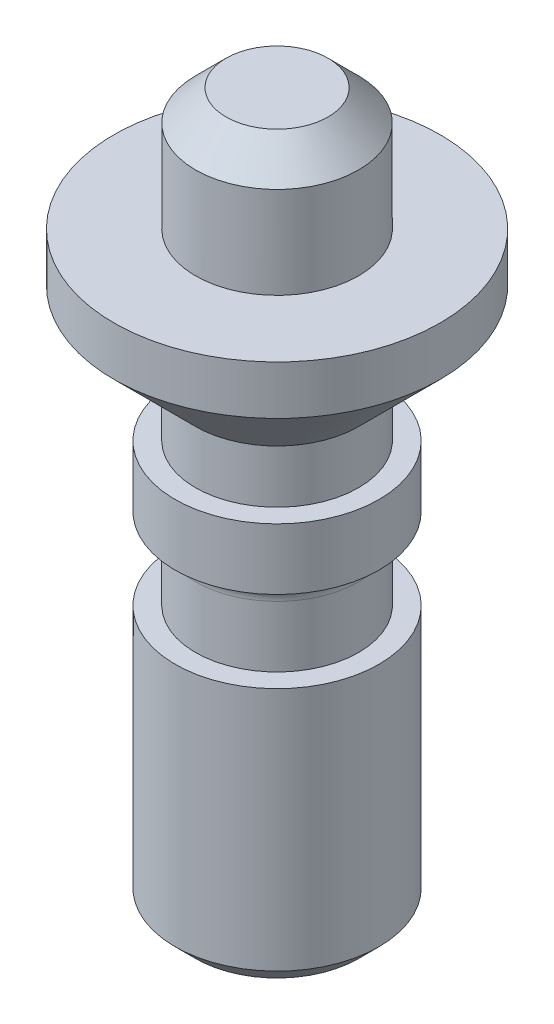
SolidWorks part; units mm, degrees
ref_plane "Front Plane" through (0, 0, 0) normal (0, 0, 1) x (1, 0, 0)
ref_plane "Top Plane" through (0, 0, 0) normal (0, 1, 0) x (1, 0, 0)
ref_plane "Right Plane" through (0, 0, 0) normal (1, 0, 0) x (0, 0, -1)
sketch "Sketch1" plane through (0, 0, 0) normal (0, 0, 1) x (1, 0, 0)
  line L0 (0, -103.4203) -> (0, 5067.5948) construction
  line L1 (0, 0) -> (2.5, 0)
  line L2 (2.5, 0) -> (2.5, 6.5)
  line L3 (2.5, 6.5) -> (2, 6.5)
  line L4 (2, 6.5) -> (2, 8.5)
  line L5 (2, 8.5) -> (2.5, 8.5)
  line L6 (2.5, 8.5) -> (2.5, 10)
  line L7 (2.5, 10) -> (2, 10)
  line L8 (2, 10) -> (2, 11.3)
  line L9 (2, 11.3) -> (4, 13.3)
  line L10 (4, 13.3) -> (4, 14.5)
  line L11 (4, 14.5) -> (2, 14.5)
  line L12 (2, 14.5) -> (2, 17.5)
  line L13 (2, 17.5) -> (0, 17.5)
  line L14 (0, 17.5) -> (0, 0)
  point P16 (1, 17.5)
  dimension "D1" = 17.5
  dimension "D2" = 3
  dimension "D3" = 4.2
  dimension "D4" = 6.5
  dimension "D5" = 8.5
  dimension "D6" = 1.5
  dimension "D7" = 1.3
  dimension "D8" = 45
  dimension "D9" = 2.5
  dimension "D10" = 2
  dimension "D11" = 2.5
  dimension "D12" = 2
  dimension "D13" = 4
  dimension "D14" = 2
revolve "Revolve1" add sketch "Sketch1" angle 360 about L0
fillet "Fillet1" radius 0.5 1 edges at (2, 8.5, 0)
chamfer "Chamfer1" distance 0.5 angle 45 1 edges at (2.5, 0, 0)
chamfer "Chamfer2" distance 0.75 angle 45 1 edges at (2, 17.5, 0)
sketch "Sketch4" plane through (0, 0, 0) normal (0, -1, 0) x (1, 0, 0)
  circle A0 centre (0, 0) radius 1.5
  dimension "D1" = 3
extrude "Cut-Extrude2" cut sketch "Sketch4" against normal blind 8.5 contours A0
sketch "Sketch6" plane through (0, 0, 0) normal (0, -1, 0) x (1, 0, 0)
  line L0 (-0.5, 1.4142) -> (-0.5, 1.1456)
  line L1 (0.5, 1.4142) -> (0.5, 1.1456)
  arc A0 (0.5, 1.1456) -> (-0.5, 1.1456) centre (0, 0) ccw
  circle A1 centre (0, 0) radius 1.5 construction
  arc A2 (0.5, 1.4142) -> (-0.5, 1.4142) centre (0, 0) ccw
  dimension "D1" = 2.5
  dimension "D2" = 0.5
  dimension "D3" = 0.5
extrude "Boss-Extrude1" add sketch "Sketch6" against normal blind 8.5
pattern_circular "CirPattern1" count 4 over 360 about axis through (0, 0.5, 0) along (0, 1, 0) of "Boss-Extrude1"
